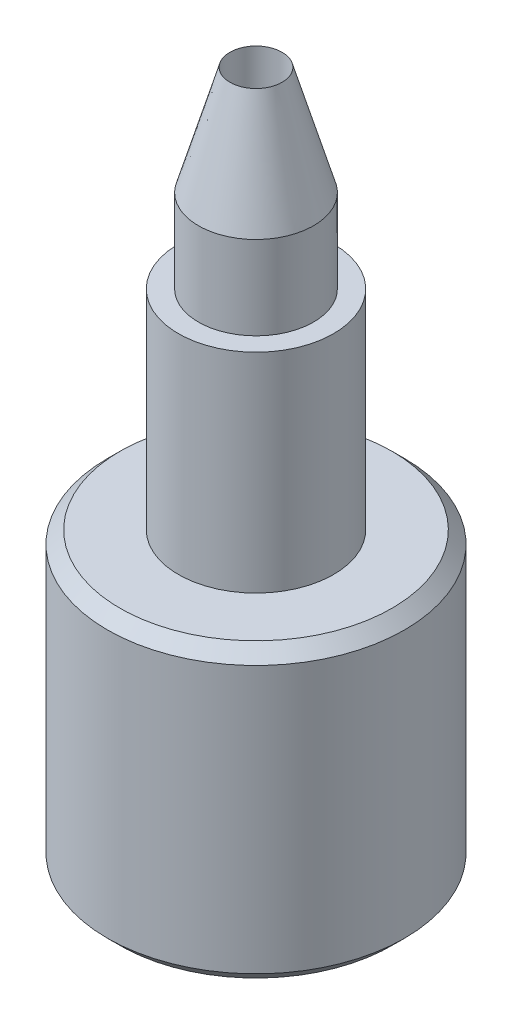
SolidWorks part; units mm, degrees
material "Polyetheretherketone (PEEK)"
ref_plane "Front Plane" through (0, 0, 0) normal (0, 0, 1) x (1, 0, 0)
ref_plane "Top Plane" through (0, 0, 0) normal (0, 1, 0) x (1, 0, 0)
ref_plane "Right Plane" through (0, 0, 0) normal (1, 0, 0) x (0, 0, -1)
ref_axis "Axis1" through (0, -1.0541, 0) along (0, 1, 0)
sketch "Sketch1" plane through (0, 0, 0) normal (0, 0, 1) x (1, 0, 0)
  line L0 (0, 0) -> (0, 21.082) construction
  line L1 (0, 21.082) -> (0.7937, 21.082)
  line L2 (0.7937, 21.082) -> (1.7526, 17.78)
  line L3 (1.7526, 17.78) -> (1.7526, 15.24)
  line L4 (2.3622, 8.89) -> (4.5212, 8.89)
  line L5 (4.5212, 8.89) -> (4.5212, 0)
  line L6 (4.5212, 0) -> (0, 0)
  line L7 (1.7526, 15.24) -> (2.3622, 15.24)
  line L8 (2.3622, 15.24) -> (2.3622, 8.89)
  line L9 (0, 0) -> (0, 21.082)
  dimension "D1" = 9.0424
  dimension "D2" = 8.89
  dimension "D3" = 21.082
  dimension "D4" = 1.5875
  dimension "D5" = 3.302
  dimension "D6" = 5.842
  dimension "D7" = 4.7244
  dimension "D8" = 3.5052
revolve "Revolve1" add sketch "Sketch1" angle 360 about L0
chamfer "Chamfer1" distance 0.381 angle 45 2 edges at (0, 0, -4.5212) (0, 8.89, -4.5212)
sketch "Sketch2" plane through (0, 0, 0) normal (0, -1, 0) x (1, 0, 0)
  circle A0 centre (0, 0) radius 2.667
  dimension "D1" = 5.334
extrude "Cut-Extrude1" cut sketch "Sketch2" against normal blind 6.35
sketch "Sketch3" plane through (0, 21.082, 0) normal (0, 1, 0) x (1, 0, 0)
  circle A1 centre (0, 0) radius 0.7937
  circle A2 centre (0, 0) radius 0.7937
  dimension "D1" = 0
extrude "Cut-Extrude2" cut sketch "Sketch3" against normal through all
sketch "Sketch4" plane through (0, 0, 0) normal (0, 1, 0) x (1, 0, 0)
  line L0 (0, 0) -> (0, 4.5212) construction
  line L1 (0, 4.5212) -> (0.127, 4.5212)
  line L2 (0, 4.5212) -> (-0.127, 4.5212)
  line L3 (0.127, 4.5212) -> (0, 4.3434)
  line L4 (-0.127, 4.5212) -> (0, 4.3434)
  circle A0 centre (0, 0) radius 4.5212 construction
  dimension "D1" = 0.254
  dimension "D2" = 0.1778
extrude "Cut-Extrude3" [suppressed] cut sketch "Sketch4" along normal through all
pattern_circular "CirPattern1" [suppressed] count 100 over 360 of bodies 108
